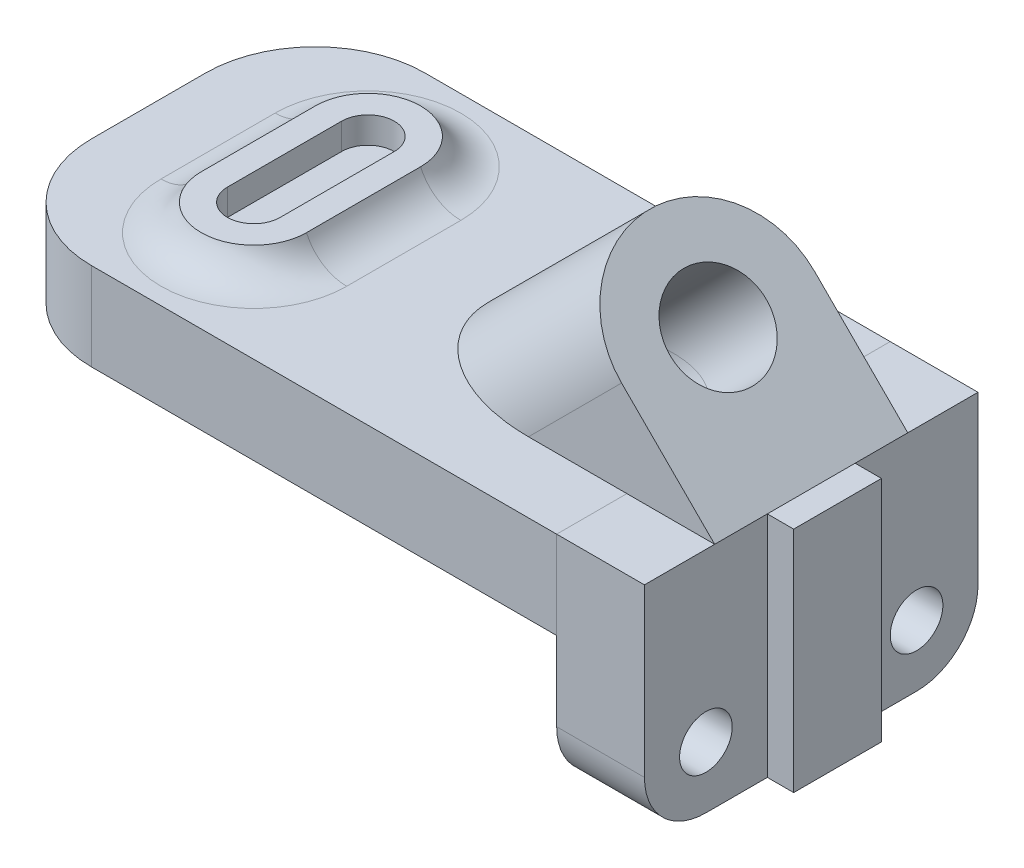
SolidWorks part; units mm, degrees
ref_plane "Front Plane" through (0, 0, 0) normal (0, 0, 1) x (1, 0, 0)
ref_plane "Top Plane" through (0, 0, 0) normal (0, 1, 0) x (1, 0, 0)
ref_plane "Right Plane" through (0, 0, 0) normal (1, 0, 0) x (0, 0, -1)
sketch "Sketch1" plane through (0, 0, 0) normal (0, 1, 0) x (1, 0, 0)
  line L0 (-70.023, 1.9044) -> (-70.023, -24.0956)
  line L1 (-45.023, 26.9044) -> (60.977, 26.9044)
  line L3 (-45.023, -49.0956) -> (60.977, -49.0956)
  line L4 (60.977, 26.9044) -> (60.977, -49.0956)
  arc A0 (-45.023, 26.9044) -> (-70.023, 1.9044) centre (-45.023, 1.9044) ccw
  arc A1 (-70.023, -24.0956) -> (-45.023, -49.0956) centre (-45.023, -24.0956) ccw
  point P10 (0, 0)
  dimension "D3" = 25
  dimension "D4" = 25
  dimension "D1" = 106
  dimension "D2" = 26
extrude "Boss-Extrude1" add sketch "Sketch1" along normal blind 20
sketch "Sketch2" plane through (0, 20, 0) normal (0, 1, 0) x (1, 0, 0)
  line L0 (-62.0649, -24.0956) -> (-33.023, -24.0956) construction
  line L2 (-45.023, 1.9044) -> (-45.023, -24.0956)
  line L4 (-21.023, 1.9044) -> (-21.023, -24.0956)
  line L5 (-61.2467, 1.9044) -> (13.1877, 1.9044) construction
  line L6 (-33.023, 13.9044) -> (-33.023, -36.0956) construction
  line L7 (-39.023, 1.9044) -> (-39.023, -24.0956)
  line L9 (-27.023, -24.0956) -> (-27.023, 1.9044)
  line L10 (-33.023, -24.0956) -> (29.3492, -24.0956) construction
  arc A0 (-45.023, 1.9044) -> (-21.023, 1.9044) centre (-33.023, 1.9044) cw
  arc A1 (-45.023, -24.0956) -> (-21.023, -24.0956) centre (-33.023, -24.0956) ccw
  arc A2 (-39.023, 1.9044) -> (-27.023, 1.9044) centre (-33.023, 1.9044) cw
  arc A3 (-39.023, -24.0956) -> (-27.023, -24.0956) centre (-33.023, -24.0956) ccw
  dimension "D2" = 12
  dimension "D4" = 12
  dimension "D1" = 26
extrude "Boss-Extrude2" add sketch "Sketch2" along normal blind 6 contours L2 A1 L4 A0 A3 L7 A2 L9 region at (-33.023, 20, -13.3498)
fillet "Fillet1" radius 10 4 edges at (-33.023, 20, -13.9044) (-45.023, 20, 11.0956) (-33.023, 20, 36.0956) (-21.023, 20, 11.0956)
sketch "Sketch3" plane through (0, 0, 49.0956) normal (0, 0, 1) x (1, 0, 0)
  line L1 (60.977, 20) -> (80.977, 20)
  line L2 (60.977, 20) -> (60.977, -32)
  line L3 (60.977, -32) -> (80.977, -32)
  line L4 (80.977, 20) -> (80.977, -32)
  dimension "D1" = 20
  dimension "D2" = 52
extrude "Boss-Extrude3" add sketch "Sketch3" against normal blind 76 separate body
fillet "Fillet2" radius 14 2 edges at (70.977, -32, -26.9044) (70.977, -32, 49.0956)
sketch "Sketch4" plane through (80.977, 0, 0) normal (1, 0, 0) x (0, 0, -1)
  line L0 (-35.0956, -32) -> (-35.0956, 20) construction
  line L1 (12.9044, -32) -> (12.9044, 20) construction
  line L2 (-49.0956, -18) -> (26.9044, -18) construction
  line L4 (26.9044, 20) -> (-49.0956, 20) construction
  line L5 (-21.0956, 20) -> (-1.0956, 20)
  line L6 (-21.0956, 20) -> (-21.0956, -32)
  line L7 (-21.0956, -32) -> (-1.0956, -32)
  line L8 (-1.0956, 20) -> (-1.0956, -32)
  line L9 (12.9044, -32) -> (-35.0956, -32) construction
  line L10 (-49.0956, -18) -> (-49.0956, 20) construction
  circle A0 centre (-35.0956, -18) radius 6
  circle A1 centre (12.9044, -18) radius 6
  point P7 (-35.0956, -18)
  point P12 (-11.0956, 20)
  point P28 (12.9044, -18)
  line M5 (-35.0956, -32) -> (12.9044, -32)
  line M8 (26.9044, 20) -> (-49.0956, 20)
  dimension "D1" = 12
  dimension "D2" = 12
  dimension "D4" = 38
  dimension "D3" = 48
  dimension "D5" = 20
extrude "Boss-Extrude4" add sketch "Sketch4" along normal blind 6 contours L8 L6 M8 M5 region at (80.977, -6, 11.0956)
ref_plane "Plane1" through (50.4885, 50.4885, 0) normal (0.7071, 0.7071, 0) x (0.7071, -0.7071, 0)
sketch "Sketch5" plane through (50.4885, 50.4885, 0) normal (0.7071, 0.7071, 0) x (0.7071, -0.7071, 0)
  line L0 (43.1173, -21.0956) -> (43.1173, -49.0956) construction
  line L1 (43.1173, -33.0956) -> (13.1173, -33.0956)
  line L2 (43.1173, -33.0956) -> (43.1173, 10.9044)
  line L3 (43.1173, 10.9044) -> (13.1173, 10.9044)
  line L5 (43.1173, -49.0956) -> (28.9751, -49.0956) construction
  arc A0 (13.1173, -33.0956) -> (13.1173, 10.9044) centre (13.1173, -11.0956) cw
  point P7 (43.1173, -11.0956)
  dimension "D1" = 22
  dimension "D2" = 38
  dimension "D3" = 30
extrude "Boss-Extrude5" add sketch "Sketch5" against normal up to surface (30 mm away) separate body up to face at (-33.023, 20, 11.0956)
sketch "Sketch7" plane through (50.4885, 50.4885, 0) normal (0.7071, 0.7071, 0) x (0, 0, -1)
  line L0 (-33.0956, -43.1173) -> (10.9044, -43.1173) construction
  line L1 (-33.0956, -13.1173) -> (-33.0956, -43.1173) construction
  circle A0 centre (-11.0956, -13.1173) radius 11
  dimension "D3" = 22
  dimension "D1" = 30
  dimension "D2" = 22
hole_wizard "Ø20.0mm Dowel Hole1" positions "3DSketch2" profile "Sketch8" hole size "Ø20.0" standard "AS"
sketch3d "3DSketch2"
  point P0 (59.7638, 41.2132, 11.0956)
sketch "Sketch8" plane through (59.7638, 41.2132, 11.0956) normal (0, 0, 1) x (-0.7071, 0.7071, 0)
  line L0 (0, 0) -> (0, 38.6095)
  line L1 (0, 38.6095) -> (11, 32)
  line L2 (11, 32) -> (11, 0)
  line L5 (11, 0) -> (0, 0)
  line L10 (0, 38.6095) -> (-11, 32) construction
  line L11 (0, -6.35) -> (0, 107.95) construction
  dimension "Hole Dia." = 22
  dimension "Hole Depth" = 32
  dimension "Drill Angle" = 118
extrude "Cut-Extrude1" cut sketch "Sketch4<3>" against normal up to next (20 mm away) contours A0
sketch "Sketch4<3>" plane through (80.977, 0, 0) normal (1, 0, 0) x (0, 0, -1) same geometry as "Sketch4"
extrude "Cut-Extrude2" cut sketch "Sketch4<4>" against normal up to next (20 mm away) contours A1
sketch "Sketch4<4>" plane through (80.977, 0, 0) normal (1, 0, 0) x (0, 0, -1) same geometry as "Sketch4"
